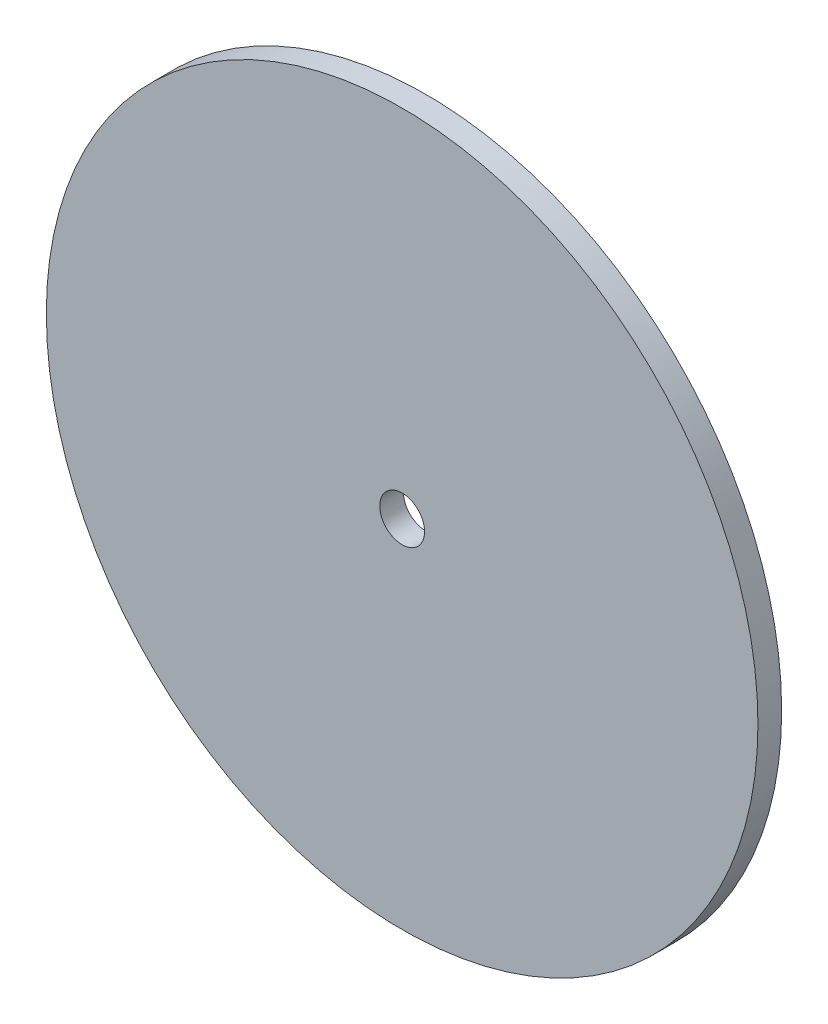
SolidWorks part; units mm, degrees
ref_plane "Front Plane" through (0, 0, 0) normal (0, 0, 1) x (1, 0, 0)
ref_plane "Top Plane" through (0, 0, 0) normal (0, 1, 0) x (1, 0, 0)
ref_plane "Right Plane" through (0, 0, 0) normal (1, 0, 0) x (0, 0, -1)
sketch "Sketch1" plane through (0, 0, 0) normal (0, 0, 1) x (1, 0, 0)
  circle A0 centre (0, 0) radius 19.05
  circle A1 centre (0, 0) radius 1.2
  dimension "D1" = 38.1
  dimension "D2" = 2.4
extrude "Boss-Extrude1" add sketch "Sketch1" along normal blind 1.27
sketch "Sketch2" plane through (0, 0, 0) normal (0, 0, -1) x (-1, 0, 0)
  line L0 (-1.524, 6.3188) -> (-1.524, 7.5888)
  line L1 (-1.524, 7.5888) -> (1.524, 7.5888)
  line L2 (1.524, 7.5888) -> (1.524, 6.3188)
  circle A0 centre (0, 0) radius 6.5
  arc A1 (-1.524, 6.3188) -> (1.524, 6.3188) centre (0, 0) cw
  point P5 (0, 7.5888)
  dimension "D1" = 13
  dimension "D2" = 1.27
  dimension "D3" = 3.048
extrude "Boss-Extrude2" add sketch "Sketch2" along normal blind 1.27 contours L2 A1 L0 L1
pattern_circular "CirPattern1" count 4 over 360 about axis through (0, 0, 1.27) along (0, 0, -1) of "Boss-Extrude2" reverse direction yes
